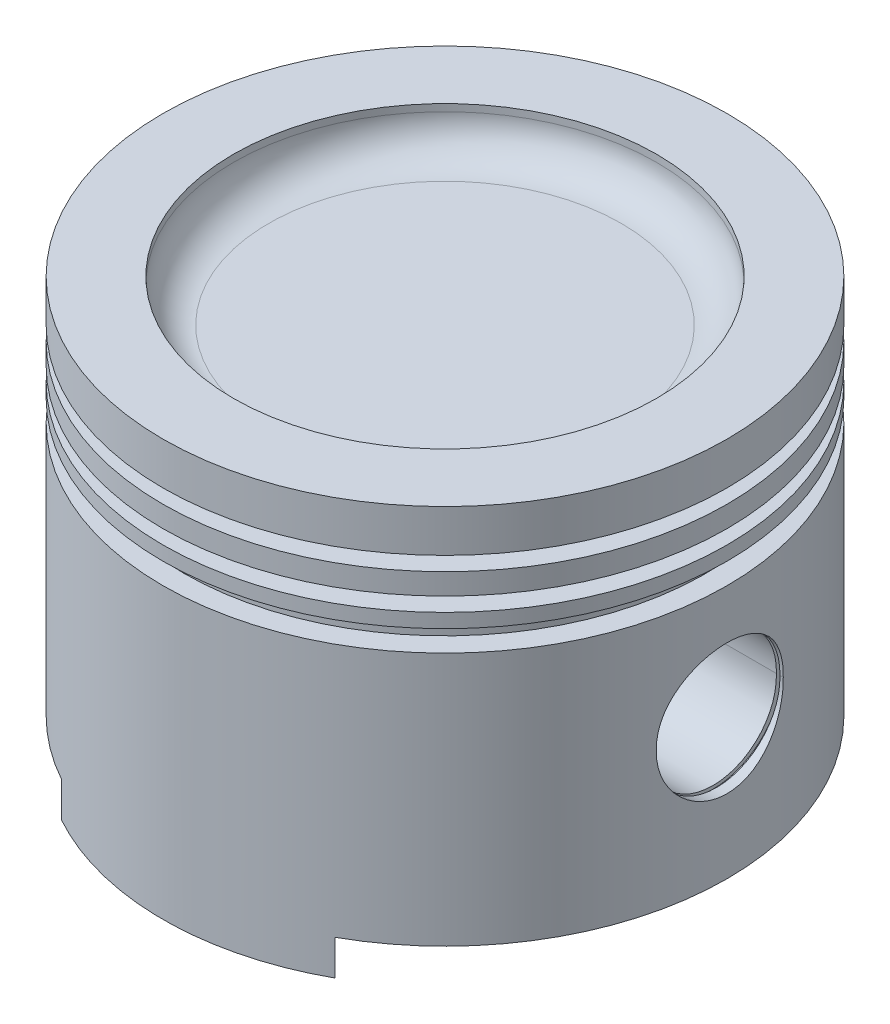
SolidWorks part; units mm, degrees
ref_plane "前视基准面" through (0, 0, 0) normal (0, 0, 1) x (1, 0, 0)
ref_plane "上视基准面" through (0, 0, 0) normal (0, 1, 0) x (1, 0, 0)
ref_plane "右视基准面" through (0, 0, 0) normal (1, 0, 0) x (0, 0, -1)
other "Configuration Table"
sketch "草图1" plane through (0, 0, 0) normal (0, 1, 0) x (1, 0, 0)
  circle A0 centre (0, 0) radius 40
extrude "凸台-拉伸1" add sketch "草图1" along normal blind 59
sketch "草图2" plane through (0, 0, 0) normal (0, -1, 0) x (-1, 0, 0)
  line L0 (-19.3649, -35) -> (19.3649, -35)
  line L1 (-19.3649, 35) -> (19.3649, 35)
  circle A0 centre (0, 0) radius 40 construction
  arc A1 (19.3649, -35) -> (19.3649, 35) centre (0, 0) ccw
  arc A2 (-19.3649, 35) -> (-19.3649, -35) centre (0, 0) ccw
  dimension "D1" = 70
extrude "切除-拉伸1" cut sketch "草图2" against normal blind 5
ref_plane "基准面1" through (40, 0, 0) normal (1, 0, 0) x (0, 0, -1)
sketch "草图4" plane through (40, 0, 0) normal (1, 0, 0) x (0, 0, -1)
  circle A0 centre (0, 25) radius 9
extrude "切除-拉伸2" cut sketch "草图4" against normal through all
sketch "草图6" plane through (0, 59, 0) normal (0, 1, 0) x (1, 0, 0)
  circle A0 centre (0, 0) radius 30
ref_plane "基准面2" through (0, 53, 0) normal (0, 1, 0) x (1, 0, 0)
sketch "草图7" plane through (0, 53, 0) normal (0, 1, 0) x (1, 0, 0)
  circle A0 centre (0, 0) radius 37
  circle A1 centre (0, 0) radius 40
extrude "切除-拉伸4" cut sketch "草图7" against normal blind 2
ref_plane "基准面3" through (0, 48, 0) normal (0, 1, 0) x (1, 0, 0)
sketch "草图8" plane through (0, 48, 0) normal (0, 1, 0) x (1, 0, 0)
  circle A0 centre (0, 0) radius 37
  circle A1 centre (0, 0) radius 40
extrude "切除-拉伸5" cut sketch "草图8" against normal blind 2
ref_plane "基准面4" through (0, 44, 0) normal (0, 1, 0) x (1, 0, 0)
sketch "草图10" plane through (0, 44, 0) normal (0, 1, 0) x (1, 0, 0)
  circle A0 centre (0, 0) radius 37
  circle A1 centre (0, 0) radius 40
extrude "切除-拉伸6" cut sketch "草图10" against normal blind 3
extrude "切除-拉伸7" cut sketch "草图6" against normal blind 6 contours A0
fillet "圆角2" radius 5 1 edges at (0, 53, 30)
sketch "草图13" plane through (0, 0, 0) normal (0, 1, 0) x (1, 0, 0)
  circle A3 centre (0, 0) radius 27
curve "曲线2"
sketch "草图4<2>" plane through (40, 0, 0) normal (1, 0, 0) x (0, 0, -1) same geometry as "草图4"
ref_plane "基准面5" through (13, 0, 0) normal (1, 0, 0) x (0, 0, -1)
sketch "草图16" plane through (13, 0, 0) normal (1, 0, 0) x (0, 0, -1)
  line L0 (-13, 25) -> (-13, 46.5)
  line L1 (13, 25) -> (13, 46.5)
  line L2 (-13, 46.5) -> (13, 46.5)
  arc A0 (-13, 25) -> (13, 25) centre (0, 25) ccw
ref_plane "基准面6" through (38, 0, 0) normal (1, 0, 0) x (0, 0, -1)
sketch "草图17" plane through (38, 0, 0) normal (1, 0, 0) x (0, 0, -1)
  circle A0 centre (0, 25) radius 10
extrude "切除-拉伸11" cut sketch "草图17" along normal blind 0.5
mirror "镜向1" about plane through (0, 0, 0) normal (1, 0, 0) of "切除-拉伸11" second plane through (0, 0, 0) second plane normal (0, 0, 1)
extrude "切除-拉伸12" cut sketch "草图13" along normal blind 46.5
extrude "凸台-拉伸2" add sketch "草图16" along normal blind 19
sketch "草图21" plane through (40, 0, 0) normal (1, 0, 0) x (0, 0, -1)
  circle A0 centre (0, 25) radius 9
extrude "切除-拉伸13" cut sketch "草图21" against normal through all
mirror "镜向2" about plane through (0, 0, 0) normal (1, 0, 0) of "凸台-拉伸2"
sketch "草图22" plane through (13, 0, 0) normal (1, 0, 0) x (0, 0, -1)
  circle A0 centre (0, 24.4518) radius 9
extrude "切除-拉伸14" cut sketch "草图22" along normal through all
mirror "镜向3" about plane through (0, 0, 0) normal (1, 0, 0) of "切除-拉伸2"
sketch "草图23" plane through (0, 46.5, 0) normal (0, -1, 0) x (1, 0, 0)
  line L6 (-13, 13) -> (-13, -13)
  line L7 (-13, -13) -> (-23.6643, -13)
  line L8 (23.6643, -13) -> (13, -13)
  line L9 (13, -13) -> (13, 13)
  line L10 (13, 13) -> (23.6643, 13)
  line L11 (-23.6643, 13) -> (-13, 13)
  arc A2 (-23.6643, -13) -> (23.6643, -13) centre (0, 0) ccw
  arc A3 (23.6643, 13) -> (-23.6643, 13) centre (0, 0) ccw
  arc A4 (-23.6643, -13) -> (23.6643, -13) centre (0, 0) ccw
  arc A5 (23.6643, 13) -> (-23.6643, 13) centre (0, 0) ccw
  dimension "D1" = 0
fillet "圆角7" radius 5 2 edges at (0, 46.5, -27) (0, 46.5, 27)
